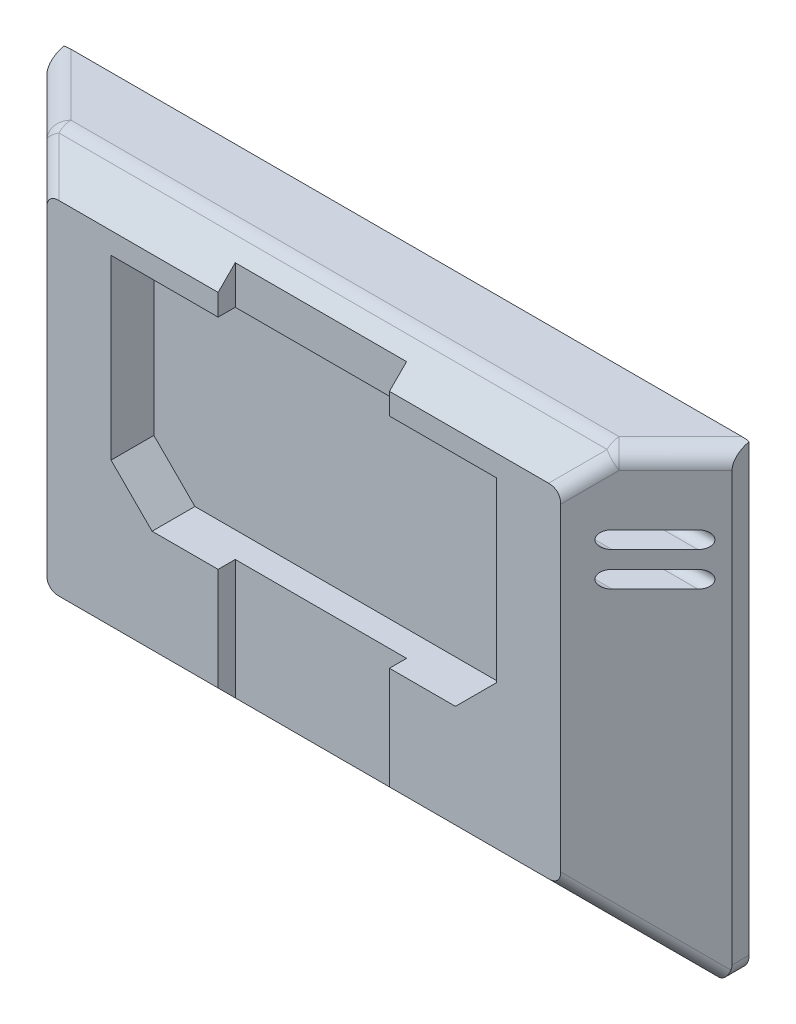
SolidWorks part; units mm, degrees
ref_plane "Front Plane" through (0, 0, 0) normal (0, 0, 1) x (1, 0, 0)
ref_plane "Top Plane" through (0, 0, 0) normal (0, 1, 0) x (1, 0, 0)
ref_plane "Right Plane" through (0, 0, 0) normal (1, 0, 0) x (0, 0, -1)
sketch "Sketch1" plane through (0, 0, 0) normal (0, 0, 1) x (1, 0, 0)
  line L1 (-40, -30) -> (40, -30)
  line L2 (-40, -30) -> (-40, 30)
  line L3 (-40, 30) -> (40, 30)
  line L4 (40, -30) -> (40, 30)
  line L5 (-40, -30) -> (40, 30) construction
  line L6 (-40, 30) -> (40, -30) construction
  point P0 (0, 0)
  dimension "D1" = 80
  dimension "D2" = 60
extrude "Boss-Extrude1" add sketch "Sketch1" along normal blind 12
chamfer "Chamfer1" distance 10 angle 45 4 edges at (-40, 0, 12) (0, 30, 12) (40, 0, 12) (0, -30, 12)
sketch "Sketch2" plane through (0, -30, 0) normal (0, -1, 0) x (1, 0, 0)
  line L0 (-30, 12) -> (30, 12) construction
  line L1 (-10, 12) -> (10, 12)
  line L2 (-10, 12) -> (-10, 10)
  line L3 (-10, 10) -> (10, 10)
  line L4 (10, 12) -> (10, 10)
  point P6 (0, 10)
  dimension "D1" = 20
  dimension "D2" = 2
extrude "Cut-Extrude1" cut sketch "Sketch2" against normal through all
sketch "Sketch3" plane through (40, 0, 0) normal (1, 0, 0) x (0, 0, -1)
  line L0 (-9, 15) -> (-4, 15) construction
  line L1 (-9, 16) -> (-4, 16)
  line L2 (-9, 14) -> (-4, 14)
  line L3 (-9, 11) -> (-4, 11) construction
  line L4 (-9, 12) -> (-4, 12)
  line L5 (-9, 10) -> (-4, 10)
  line L6 (-2, 30) -> (-2, -30) construction
  arc A0 (-9, 16) -> (-9, 14) centre (-9, 15) ccw
  arc A1 (-4, 14) -> (-4, 16) centre (-4, 15) ccw
  arc A2 (-9, 12) -> (-9, 10) centre (-9, 11) ccw
  arc A3 (-4, 10) -> (-4, 12) centre (-4, 11) ccw
  point P2 (-6.5, 15)
  point P9 (-6.5, 11)
  dimension "D3" = 1
  dimension "D4" = 1
  dimension "D1" = 5
  dimension "D2" = 5
  dimension "D5" = 4
  dimension "D6" = 15
  dimension "D7" = 2
  dimension "D8" = 2
fillet "Fillet1" radius 2 8 edges at (40, 30, 1) (35, 25, 7) (-35, 25, 7) (-40, 30, 1) (-35, -25, 7) (-40, -30, 1) (35, -25, 7) (40, -30, 1)
sketch "Sketch4" plane through (0, 0, 12) normal (0, 0, 1) x (1, 0, 0)
  line L0 (-22, 17) -> (-22, -3)
  line L1 (-22, -3) -> (-17.5, -7.5)
  line L2 (-17.5, -7.5) -> (17.5, -7.5)
  line L3 (17.5, -7.5) -> (22, -3)
  line L4 (22, -3) -> (22, 17)
  line L10 (-22, 17) -> (22, 17)
  line L11 (28.5858, 20) -> (10, 20) construction
  point P6 (0, -7.5)
  dimension "D1" = 3
  dimension "D2" = 20
  dimension "D3" = 35
  dimension "D4" = 44
  dimension "D5" = 7.5
  dimension "D6" = 4.5
  dimension "D7" = 4.5
  dimension "D8" = 20
  dimension "D9" = 4.5
extrude "Cut-Extrude3" cut sketch "Sketch4" against normal blind 5
sketch "Sketch5" plane through (-40, 0, 0) normal (-1, 0, 0) x (0, 0, 1)
  line L1 (0, 30) -> (10, 30)
  line L2 (0, 30) -> (0, 24)
  line L3 (0, 24) -> (10, 24)
  line L4 (10, 30) -> (10, 24)
  dimension "D1" = 10
  dimension "D2" = 6
extrude "Cut-Extrude4" cut sketch "Sketch5" against normal through all
fillet "Fillet2" radius 2 5 edges at (-37.7071, 24, 4.2929) (-34, 24, 7.6211) (37.7071, 24, 4.2929) (34, 24, 7.6211) (0, 24, 8)
sketch "Sketch6" plane through (0, 0, 12) normal (0, 0, 1) x (1, 0, 0)
  line L0 (22, 17) -> (-22, 17) construction
  line L1 (-22, 17) -> (-22, -3) construction
  line L2 (-22, -3) -> (-17.5, -7.5) construction
  line L3 (-17.5, -7.5) -> (17.5, -7.5) construction
  line L4 (17.5, -7.5) -> (22, -3) construction
  line L5 (22, -3) -> (22, 17) construction
  line L6 (22, 17) -> (-22, 17)
  line L7 (-22, 17) -> (-22, -3)
  line L8 (-22, -3) -> (-17.5, -7.5)
  line L9 (-17.5, -7.5) -> (17.5, -7.5)
  line L10 (17.5, -7.5) -> (22, -3)
  line L11 (22, -3) -> (22, 17)
  line L12 (22, 17) -> (-22, 17) construction
  line L13 (-22, 17) -> (-22, -3) construction
  line L14 (-22, -3) -> (-17.5, -7.5) construction
  line L15 (-17.5, -7.5) -> (17.5, -7.5) construction
  line L16 (17.5, -7.5) -> (22, -3) construction
  line L17 (22, -3) -> (22, 17) construction
  line L18 (22.5, 17.5) -> (-22.5, 17.5)
  line L19 (-22.5, 17.5) -> (-22.5, -3.2071)
  line L20 (-22.5, -3.2071) -> (-17.7071, -8)
  line L21 (-17.7071, -8) -> (17.7071, -8)
  line L22 (17.7071, -8) -> (22.5, -3.2071)
  line L23 (22.5, -3.2071) -> (22.5, 17.5)
  dimension "D1" = 0
  dimension "D2" = 0
  dimension "D3" = 0.5
extrude "Cut-Extrude5" cut sketch "Sketch6" against normal up to surface (5 mm away) contours L18 L19 L20 L21 L22 L23 up to face at (0, 2.1667, 7)
extrude "Cut-Extrude6" cut sketch "Sketch3" against normal blind 10
